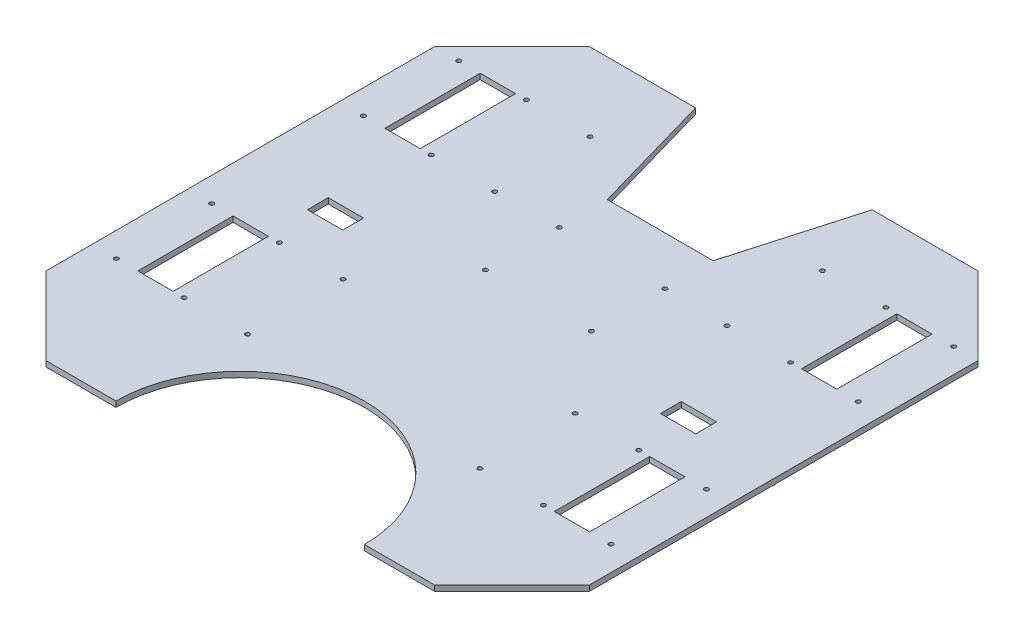
SolidWorks part; units mm, degrees
ref_plane "前视基准面" through (0, 0, 0) normal (0, 0, 1) x (1, 0, 0)
ref_plane "上视基准面" through (0, 0, 0) normal (0, 1, 0) x (1, 0, 0)
ref_plane "右视基准面" through (0, 0, 0) normal (1, 0, 0) x (0, 0, -1)
other "Configuration Table"
sketch "草图1" plane through (0, 0, 0) normal (0, 1, 0) x (1, 0, 0)
  line L1 (139.7, -195.58) -> (89.408, -195.58)
  line L2 (195.58, -139.7) -> (195.58, 139.7)
  line L3 (139.7, 195.58) -> (63.5, 195.58)
  line L4 (-195.58, -139.7) -> (-195.58, 139.7)
  line L8 (-139.7, 195.58) -> (-195.58, 139.7)
  line L9 (139.7, 195.58) -> (195.58, 139.7)
  line L10 (195.58, -139.7) -> (139.7, -195.58)
  line L11 (-139.7, -195.58) -> (-195.58, -139.7)
  line L13 (-89.408, -195.58) -> (-139.7, -195.58)
  line L14 (-89.408, -195.58) -> (89.408, -195.58) construction
  line L19 (-38.1, 106.68) -> (38.1, 106.68)
  line L20 (-63.5, 195.58) -> (-139.7, 195.58)
  line L21 (-63.5, 195.58) -> (-38.1, 106.68)
  line L22 (63.5, 195.58) -> (38.1, 106.68)
  line L23 (-162.56, 139.7) -> (-137.16, 139.7)
  line L24 (-162.56, 139.7) -> (-162.56, 71.12)
  line L25 (-137.16, 139.7) -> (-137.16, 71.12)
  line L26 (-162.56, 71.12) -> (-137.16, 71.12)
  line L35 (137.16, 71.12) -> (162.56, 71.12)
  line L36 (137.16, 71.12) -> (137.16, 139.7)
  line L37 (162.56, 71.12) -> (162.56, 139.7)
  line L38 (137.16, 139.7) -> (162.56, 139.7)
  line L39 (162.56, -38.1) -> (137.16, -38.1)
  line L40 (162.56, -38.1) -> (162.56, -106.68)
  line L41 (137.16, -38.1) -> (137.16, -106.68)
  line L42 (162.56, -106.68) -> (137.16, -106.68)
  line L51 (-162.56, -106.68) -> (-137.16, -106.68)
  line L52 (-162.56, -106.68) -> (-162.56, -38.1)
  line L53 (-137.16, -106.68) -> (-137.16, -38.1)
  line L54 (-162.56, -38.1) -> (-137.16, -38.1)
  line L55 (-139.7, -7.5) -> (-114.3, -7.5)
  line L56 (-139.7, -7.5) -> (-139.7, 7.5)
  line L57 (-114.3, -7.5) -> (-114.3, 7.5)
  line L58 (-139.7, 7.5) -> (-114.3, 7.5)
  line L59 (114.3, -7.5) -> (139.7, -7.5)
  line L60 (114.3, -7.5) -> (114.3, 7.5)
  line L61 (139.7, -7.5) -> (139.7, 7.5)
  line L62 (114.3, 7.5) -> (139.7, 7.5)
  arc A0 (89.408, -195.58) -> (-89.408, -195.58) centre (0, -195.58) ccw
  circle A1 centre (-83.566, 139.7) radius 1.55
  circle A2 centre (-129.286, 139.7) radius 1.55
  circle A5 centre (-83.566, -106.68) radius 1.55
  circle A6 centre (-129.286, -106.68) radius 1.55
  circle A7 centre (83.566, 139.7) radius 1.55
  circle A8 centre (129.286, 139.7) radius 1.55
  circle A9 centre (83.566, -106.68) radius 1.55
  circle A10 centre (129.286, -106.68) radius 1.55
  circle A11 centre (-129.286, 71.12) radius 1.55
  circle A12 centre (-83.566, 71.12) radius 1.55
  circle A13 centre (83.566, 71.12) radius 1.55
  circle A14 centre (129.286, 71.12) radius 1.55
  circle A15 centre (-129.286, -38.1) radius 1.55
  circle A16 centre (-83.566, -38.1) radius 1.55
  circle A17 centre (83.566, -38.1) radius 1.55
  circle A18 centre (129.286, -38.1) radius 1.55
  circle A19 centre (-178, -38.1) radius 1.55
  circle A20 centre (-178, -106.68) radius 1.55
  circle A21 centre (178, -106.68) radius 1.55
  circle A22 centre (178, -38.1) radius 1.55
  circle A23 centre (-178, 139.7) radius 1.55
  circle A24 centre (-178, 71.12) radius 1.55
  circle A25 centre (178, 139.7) radius 1.55
  circle A26 centre (178, 71.12) radius 1.55
  circle A27 centre (-38.1, 72) radius 1.55
  circle A28 centre (38.1, 72) radius 1.55
  circle A29 centre (-38.1, 19) radius 1.55
  circle A30 centre (38.1, 19) radius 1.55
  point P0 (0, 0)
  point P1 (139.7, 195.58)
  point P2 (0, -195.58)
  point P5 (-139.7, 195.58)
  point P6 (-195.58, 139.7)
  point P9 (-167.64, 167.64)
  point P10 (0, 0)
  point P11 (195.58, 139.7)
  point P12 (195.58, -139.7)
  point P13 (139.7, -195.58)
  point P14 (-139.7, -195.58)
  point P15 (-195.58, -139.7)
  point P27 (-63.5, 195.58)
  point P28 (63.5, 195.58)
  point P49 (-127, -38.1)
  point P52 (-162.56, -106.68)
  dimension "D14" = 89.408
  dimension "D28" = 3.1
  dimension "D29" = 3.1
  dimension "D34" = 3.1
  dimension "D35" = 3.1
  dimension "D38" = 3.1
  dimension "D39" = 3.1
  dimension "D46" = 3.1
  dimension "D47" = 3.1
  dimension "D56" = 3.1
  dimension "D57" = 3.1
  dimension "D73" = 3.1
  dimension "D74" = 3.1
  dimension "D79" = 3.1
  dimension "D80" = 3.1
  dimension "D85" = 3.1
  dimension "D86" = 3.1
  dimension "D94" = 3.1
  dimension "D95" = 3.1
  dimension "D102" = 3.1
  dimension "D103" = 3.1
  dimension "D106" = 3.1
  dimension "D108" = 3.1
  dimension "D116" = 3.1
  dimension "D117" = 3.1
  dimension "D118" = 3.1
  dimension "D119" = 3.1
  dimension "D120" = 3.1
  dimension "D121" = 3.1
  dimension "D1" = 195.58
  dimension "D2" = 195.58
  dimension "D3" = 139.7
  dimension "D4" = 139.7
  dimension "D5" = 195.58
  dimension "D6" = 195.58
  dimension "D7" = 139.7
  dimension "D8" = 139.7
  dimension "D9" = 139.7
  dimension "D10" = 139.7
  dimension "D11" = 139.7
  dimension "D12" = 139.7
  dimension "D13" = 89.408
  dimension "D15" = 89.408
  dimension "D16" = 195.58
  dimension "D17" = 195.58
  dimension "D18" = 25.4
  dimension "D19" = 25.4
  dimension "D20" = 106.68
  dimension "D21" = 139.7
  dimension "D22" = 139.7
  dimension "D23" = 76.2
  dimension "D24" = 63.5
  dimension "D25" = 63.5
  dimension "D26" = 83.566
  dimension "D27" = 129.286
  dimension "D30" = 83.566
  dimension "D31" = 129.286
  dimension "D32" = 106.68
  dimension "D33" = 106.68
  dimension "D36" = 83.566
  dimension "D37" = 129.286
  dimension "D40" = 139.7
  dimension "D41" = 139.7
  dimension "D42" = 106.68
  dimension "D43" = 106.68
  dimension "D44" = 83.566
  dimension "D45" = 129.286
  dimension "D48" = 137.16
  dimension "D49" = 162.56
  dimension "D50" = 71.12
  dimension "D51" = 127
  dimension "D52" = 38.1
  dimension "D53" = 137.16
  dimension "D54" = 38.1
  dimension "D55" = 106.68
  dimension "D58" = 71.12
  dimension "D59" = 129.286
  dimension "D60" = 162.56
  dimension "D61" = 137.16
  dimension "D62" = 162.56
  dimension "D63" = 139.7
  dimension "D64" = 137.16
  dimension "D65" = 106.68
  dimension "D66" = 162.56
  dimension "D67" = 83.566
  dimension "D68" = 71.12
  dimension "D69" = 71.12
  dimension "D70" = 71.12
  dimension "D71" = 129.286
  dimension "D72" = 83.566
  dimension "D75" = 83.566
  dimension "D76" = 129.286
  dimension "D77" = 38.1
  dimension "D78" = 38.1
  dimension "D81" = 38.1
  dimension "D82" = 38.1
  dimension "D83" = 83.566
  dimension "D84" = 129.286
  dimension "D87" = 7.5
  dimension "D88" = 7.5
  dimension "D89" = 25.4
  dimension "D90" = 139.7
  dimension "D91" = 114.3
  dimension "D92" = 139.7
  dimension "D93" = 7.5
  dimension "D96" = 178
  dimension "D97" = 178
  dimension "D98" = 38.1
  dimension "D99" = 106.68
  dimension "D100" = 38.1
  dimension "D101" = 106.68
  dimension "D104" = 178
  dimension "D105" = 178
  dimension "D107" = 139.7
  dimension "D109" = 71.12
  dimension "D110" = 178
  dimension "D111" = 178
  dimension "D112" = 178
  dimension "D113" = 178
  dimension "D114" = 139.7
  dimension "D115" = 71.12
  dimension "D122" = 38.1
  dimension "D123" = 38.1
  dimension "D124" = 19
  dimension "D125" = 72
  dimension "D126" = 38.1
  dimension "D127" = 38.1
  dimension "D128" = 19
  dimension "D129" = 72
extrude "凸台-拉伸1" add sketch "草图1" along normal blind 4 contours L4 L8 L20 L21 L19 L22 L3 L9 L2 L10 L1 A0 L13 L11
extrude "切除-拉伸2" cut sketch "草图1<4>" along normal blind 4 flip side to cut
sketch "草图1<4>" plane through (0, 0, 0) normal (0, 1, 0) x (1, 0, 0) same geometry as "草图1"
